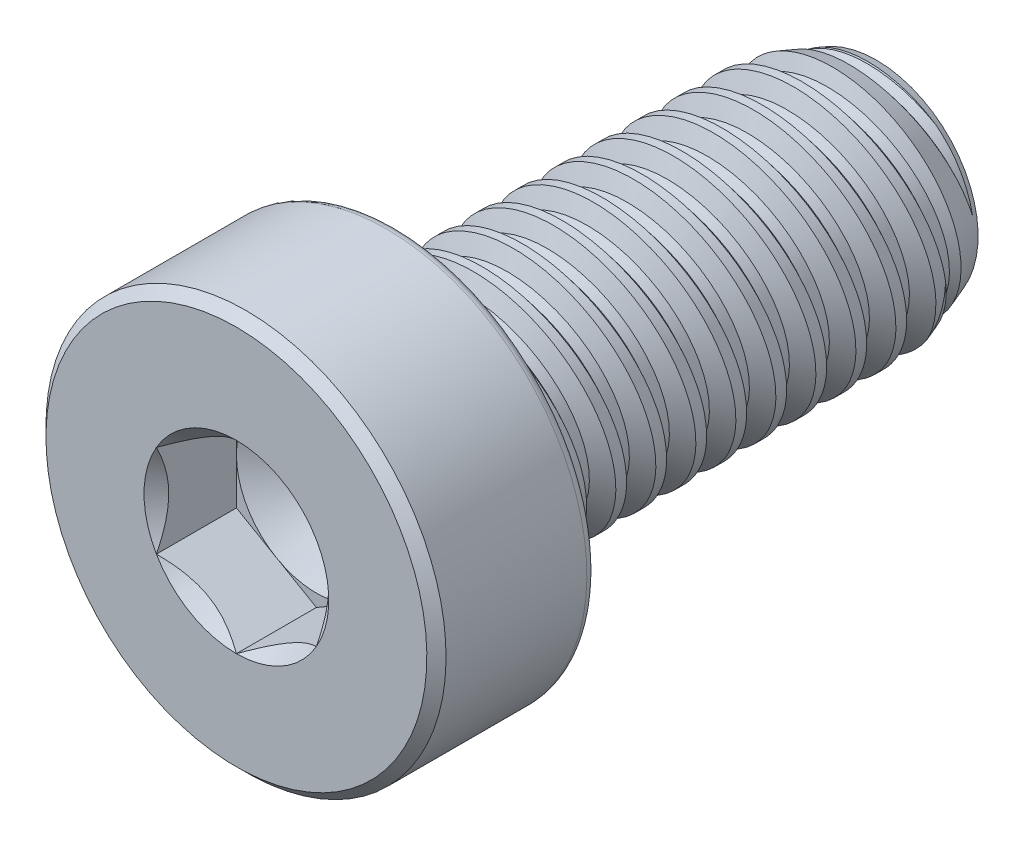
SolidWorks part; units mm, degrees
ref_plane "Front" through (0, 0, 0) normal (0, 0, 1) x (1, 0, 0)
ref_plane "Top" through (0, 0, 0) normal (0, 1, 0) x (1, 0, 0)
ref_plane "Right" through (0, 0, 0) normal (1, 0, 0) x (0, 0, -1)
sketch "Sketch1" plane through (0, 0, 0) normal (1, 0, 0) x (0, 0, -1)
  line L0 (0, 0) -> (-4, 0) construction
  line L1 (0, 0) -> (12, 0)
  line L2 (0, 0) -> (0, 3)
  line L3 (0, 3) -> (12, 3)
  line L4 (12, 0) -> (12, 3)
  line L5 (0, -3) -> (12, -3) construction
  line L6 (-4, 5) -> (-4, -5) construction
  line L7 (-4, 0) -> (-8, 0) construction
  dimension "Thread Dia" = 6
  dimension "Min Thread Length" = 12
  dimension "Head Height" = 4
  dimension "Head Dia" = 10
revolve "Revolve1" add sketch "Sketch1" angle 360 about L0
sketch "Sketch2" plane through (0, 0, 0) normal (1, 0, 0) x (0, 0, -1)
  line L0 (0, 3) -> (0, -3) construction
  line L1 (0, -3) -> (1, -3) construction
  line L2 (1, -3) -> (0, 3) construction
  line L3 (0, 3) -> (0.1233, 3.0205) construction
  line L4 (0.1233, 3.0205) -> (0.9864, 3.1644)
  line L5 (0.9864, 3.1644) -> (0.7671, 2.5791)
  line L6 (0.7671, 2.5791) -> (0.5205, 2.538)
  line L7 (0.5205, 2.538) -> (0.1233, 3.0205)
  line L8 (0.6438, 2.5586) -> (0.5548, 3.0925) construction
  line L9 (0, -3) -> (12, -3) construction
  line L10 (0, 3) -> (12, 3) construction
  line L12 (0.5703, 3) -> (1.5703, -3) construction
  line L13 (0, -0.1784) -> (2.1405, 0.1784) construction
  line L15 (0, 0) -> (0, 3) construction
  point P19 (1.0703, 0)
  dimension "D1" = 60
  dimension "Thread Pitch" = 1
  dimension "D2" = 0.125
  dimension "D3" = 0.25
  dimension "D4" = 1
revolve "Cut-Revolve1" cut sketch "Sketch2" angle 360 about L13
sketch "Sketch3" plane through (0, 0, 0) normal (1, 0, 0) x (0, 0, -1)
  line L0 (12, 2.538) -> (10.7307, 3)
  line L1 (10.7307, 3) -> (12, 3)
  line L2 (12, 3) -> (12, 2.538)
  line L3 (0, 3) -> (12, 3) construction
  line L4 (12, 0) -> (12, 3) construction
  line L5 (10.7307, 0) -> (0, 0) construction
  line L6 (10.7307, 3) -> (10.7307, -3) construction
  line L7 (0, -3) -> (12, -3) construction
  dimension "D1" = 20
  dimension "D2" = 6
revolve "Cut-Revolve2" cut sketch "Sketch3" angle 360 about L5
pattern_linear "LPattern1" count 12 spacing 1 along (0, 0, 1) count 2 spacing 1 along (0, 0, 1)
ref_plane "Plane1" through (0, 0, 0) normal (0, 0, 1) x (1, 0, 0)
sketch "Sketch4" plane through (0, 0, 0) normal (0, 0, 1) x (1, 0, 0)
  circle A0 centre (0, 0) radius 5
  dimension "D1" = 10
extrude "Extrude1" add sketch "Sketch4" along normal up to vertex
sketch "Sketch10" plane through (0, 0, 0) normal (1, 0, 0) x (0, 0, -1)
  line L0 (-4, 4.76) -> (-3.76, 5)
  line L1 (-3.76, 5) -> (-0.24, 5)
  line L2 (0, 4.76) -> (0.1, 4.76)
  line L3 (0.1, 4.76) -> (0.1, 5.1)
  line L4 (0.1, 5.1) -> (-4, 5.1)
  line L5 (-4, 5.1) -> (-4, 4.76)
  line L7 (0, 5) -> (-4, 5) construction
  line L9 (0, 4.76) -> (-4, 4.76) construction
  line L10 (-4, 0) -> (-8, 0) construction
  line L11 (0, -5) -> (0, 5) construction
  line L12 (-4, 5) -> (-4, -5) construction
  arc A0 (-0.24, 5) -> (0, 4.76) centre (-0.24, 4.76) cw
  dimension "D1" = 45
  dimension "D2" = 0.1
  dimension "D3" = 0.1
  dimension "D4" = 0.24
  dimension "D5" = 4
  dimension "D6" = 12
revolve "Cut-Revolve3" cut sketch "Sketch10" angle 360 about L10
sketch "Sketch6" plane through (0, 0, 4) normal (0, 0, 1) x (1, 0, 0)
  line L1 (0, -2.3094) -> (2, -1.1547)
  line L2 (2, -1.1547) -> (2, 1.1547)
  line L3 (2, 1.1547) -> (0, 2.3094)
  line L4 (0, 2.3094) -> (-2, 1.1547)
  line L5 (-2, 1.1547) -> (-2, -1.1547)
  line L6 (-2, -1.1547) -> (0, -2.3094)
  circle A0 centre (0, 0) radius 2 construction
  dimension "Hex" = 4
extrude "Cut-Extrude1" cut sketch "Sketch6" against normal blind 2
sketch "Sketch7" plane through (0, 0, 4) normal (0, 0, 1) x (1, 0, 0)
  circle A0 centre (0, 0) radius 2.3094
extrude "Cut-Extrude4" cut sketch "Sketch7" against normal blind 2 draft 45
sketch "Sketch8" plane through (0, 0, 2) normal (0, 0, 1) x (1, 0, 0)
  circle A0 centre (0, 0) radius 2 construction
  circle A1 centre (0, 0) radius 2
extrude "Cut-Extrude5" cut sketch "Sketch8" against normal blind 0.6667 draft 60
equation "\"D2@Sketch2\"=\"Thread Pitch@Sketch2\"/8"
equation "\"D3@Sketch2\"=\"Thread Pitch@Sketch2\"/4"
equation "\"D4@Sketch2\"=\"Thread Pitch@Sketch2\""
equation "\"D3@LPattern1\"=\"Thread Pitch@Sketch2\""
equation "\"D1@Cut-Extrude4\"=\"D1@Cut-Extrude1\""
equation "\"D1@Cut-Extrude5\"=\"D1@Cut-Extrude1\"/3"
equation "\"D1@LPattern1\"=\"Min Thread Length@Sketch1\"/\"Thread Pitch@Sketch2\""
equation "\"D4@LPattern1\"=\"Thread Pitch@Sketch2\""
equation "\"D4@Sketch10\"=\"Thread Dia@Sketch1\"/25"
equation "\"D1@Cut-Extrude1\"=\"Head Height@Sketch1\"/2"
